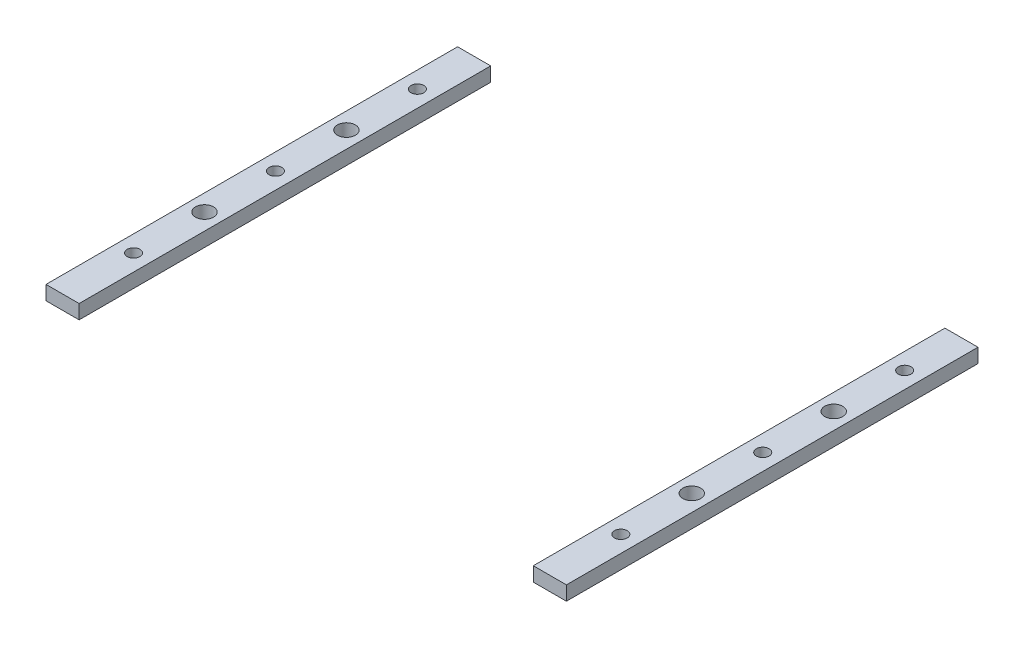
SolidWorks part; units mm, degrees
ref_plane "Front Plane" through (0, 0, 0) normal (0, 0, 1) x (1, 0, 0)
ref_plane "Top Plane" through (0, 0, 0) normal (0, 1, 0) x (1, 0, 0)
ref_plane "Right Plane" through (0, 0, 0) normal (1, 0, 0) x (0, 0, -1)
sketch "Sketch1" plane through (0, 0, 0) normal (0, 1, 0) x (1, 0, 0)
  line L0 (110, 87) -> (110, 0) construction
  line L1 (0, 0) -> (7, 0)
  line L2 (0, 0) -> (0, 87)
  line L3 (0, 87) -> (7, 87)
  line L4 (7, 0) -> (7, 87)
  line L5 (103, 0) -> (103, 87)
  line L6 (110, 0) -> (110, 87)
  line L7 (103, 87) -> (110, 87)
  line L8 (103, 0) -> (110, 0)
  line L9 (0, 0) -> (110, 0) construction
  line L10 (0, 0) -> (0, 87) construction
  line L11 (0, 87) -> (110, 87) construction
  circle A0 centre (3.5, 15) radius 1.35
  circle A1 centre (3.5, 30) radius 1.35
  circle A2 centre (3.5, 45) radius 1.35
  circle A3 centre (3.5, 60) radius 1.35
  circle A4 centre (3.5, 75) radius 1.35
  circle A5 centre (106.5, 15) radius 1.35
  circle A6 centre (106.5, 30) radius 1.35
  circle A7 centre (106.5, 75) radius 1.35
  circle A8 centre (106.5, 60) radius 1.35
  circle A9 centre (106.5, 45) radius 1.35
  dimension "D1" = 2
  dimension "D2" = 5
extrude "spacer-rails" add sketch "Sketch1" along normal blind 3
sketch "Sketch2" plane through (0, 0, 0) normal (0, -1, 0) x (1, 0, 0)
  circle A0 centre (3.5, -30) radius 1.9
  circle A2 centre (3.5, -30) radius 1.35 construction
  circle A3 centre (106.5, -30) radius 1.9
  circle A4 centre (106.5, -60) radius 1.9
  circle A5 centre (3.5, -60) radius 1.9
  dimension "D1" = 2
  dimension "D2" = 2
extrude "Cut-Extrude2" cut sketch "Sketch2" against normal through all
sketch "Sketch3" plane through (0, 0, 0) normal (0, -1, 0) x (1, 0, 0)
  circle A0 centre (3.5, -15) radius 1.9
  circle A1 centre (106.5, -15) radius 1.9
  circle A2 centre (106.5, -45) radius 1.9
  circle A3 centre (106.5, -75) radius 1.9
  circle A4 centre (3.5, -45) radius 1.9
  circle A5 centre (3.5, -75) radius 1.9
  dimension "D1" = 2
  dimension "D2" = 3
extrude "Cut-Extrude3" [suppressed] cut sketch "Sketch3" against normal through all
sketch "Sketch4" [suppressed] plane through (0, 0, 0) normal (0, -1, 0) x (1, 0, 0)
  circle A0 centre (3.5, -30) radius 3.25
  circle A1 centre (106.5, -30) radius 3.25
  circle A2 centre (106.5, -60) radius 3.25
  circle A3 centre (3.5, -60) radius 3.25
  dimension "D1" = 2
  dimension "D2" = 2
extrude "Cut-Extrude4" [suppressed] cut sketch "Sketch4" against normal blind 8.5
sketch "Sketch5" [suppressed] plane through (0, 5.41, 0) normal (0, 1, 0) x (1, 0, 0)
  circle A0 centre (3.5, 15) radius 3.25
  circle A1 centre (106.5, 15) radius 3.25
  circle A2 centre (106.5, 45) radius 3.25
  circle A3 centre (106.5, 75) radius 3.25
  circle A4 centre (3.5, 45) radius 3.25
  circle A5 centre (3.5, 75) radius 3.25
  dimension "D1" = 2
  dimension "D2" = 3
extrude "Cut-Extrude5" [suppressed] cut sketch "Sketch5" against normal blind 3.6
ref_axis "SouthWest" [suppressed] through (3.5, 7.25, -15) along (0, -1, 0)
ref_axis "NorthEast" [suppressed] through (106.5, 12.25, -75) along (0, -1, 0)
ref_plane "horizontal-center-of-spacers" through (0, 1.5, 0) normal (0, 1, 0) x (1, 0, 0)
sketch "Sketch6" [suppressed] plane through (0, 0, -87) normal (0, 0, -1) x (-1, 0, 0)
  line L0 (-103, 14.25) -> (-105, 14.25)
  line L2 (-105, 14.25) -> (-105, 15.75)
  line L3 (-110, 15.75) -> (-103, 15.75) construction
  line L4 (-103, 15.75) -> (-103, 0) construction
  line L5 (-7, 14.25) -> (-5, 14.25)
  line L6 (-7, 15.75) -> (-7, 0) construction
  line L7 (-5, 14.25) -> (-5, 15.75)
  line L8 (-7, 15.75) -> (0, 15.75) construction
  line L9 (-105, 15.75) -> (-5, 15.75)
  line L10 (-7, 14.25) -> (-103, 14.25)
extrude "Cut-Extrude6" [suppressed] cut sketch "Sketch6" against normal through all contours L10 L0 L2 L9 L7 L5
sketch "Sketch7" plane through (0, 0, 0) normal (0, -1, 0) x (1, 0, 0)
  circle A0 centre (3.5, -60) radius 3.175
  circle A1 centre (3.5, -30) radius 3.175
  circle A2 centre (106.5, -30) radius 3.175
  circle A3 centre (106.5, -60) radius 3.175
extrude "Cut-Extrude7" [suppressed] cut sketch "Sketch7" against normal blind 1
